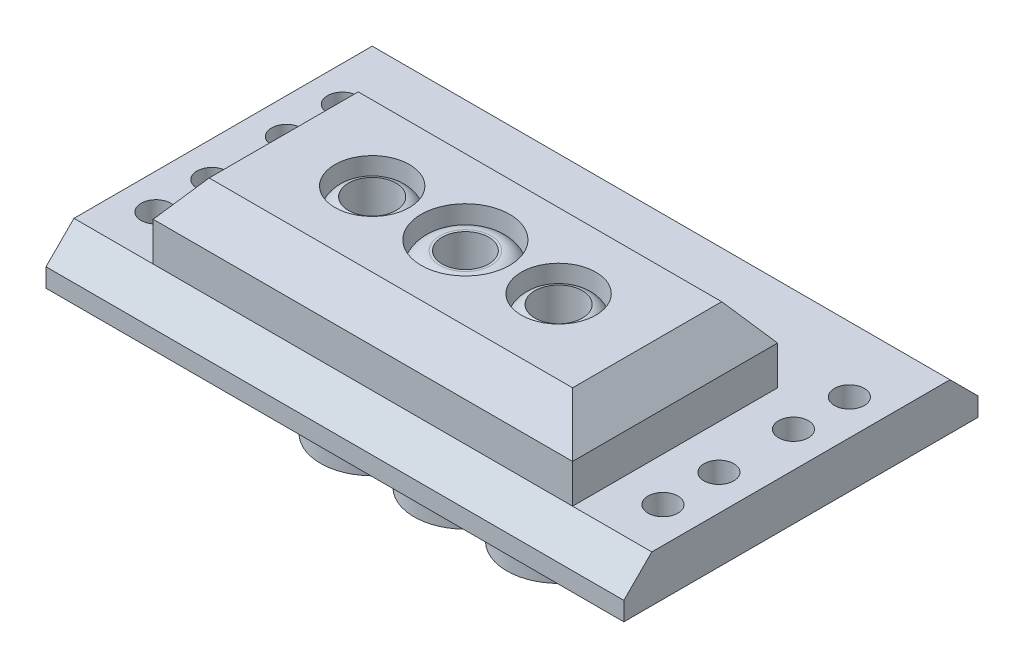
SolidWorks part; units mm, degrees
ref_plane "Alzado" through (0, 0, 0) normal (0, 0, 1) x (1, 0, 0)
ref_plane "Planta" through (0, 0, 0) normal (0, 1, 0) x (1, 0, 0)
ref_plane "Vista lateral" through (0, 0, 0) normal (1, 0, 0) x (0, 0, -1)
sketch "Croquis1" plane through (0, 0, 0) normal (0, 1, 0) x (1, 0, 0)
  line L0 (27.2, -5) -> (27.2, -11) construction
  line L1 (-31, -19) -> (31, -19)
  line L2 (-31, -19) -> (-31, 19)
  line L3 (-31, 19) -> (31, 19)
  line L4 (31, -19) -> (31, 19)
  line L5 (-31, -19) -> (31, 19) construction
  line L6 (-31, 19) -> (31, -19) construction
  line L7 (27.2, -11) -> (-27.2, -11) construction
  line L8 (-27.2, -5) -> (-27.2, -11) construction
  line L9 (27.2, 9) -> (27.2, 3) construction
  line L10 (27.2, 9) -> (27.2, 19) construction
  line L11 (27.2, 9) -> (31, 9) construction
  line L12 (-27.2, 9) -> (-27.2, 3) construction
  line L13 (-27.2, 9) -> (-27.2, 19) construction
  line L14 (0, 0) -> (0, -5) construction
  line L15 (-10, -5) -> (10, -5) construction
  circle A0 centre (27.2, -11) radius 1.6
  circle A1 centre (27.2, -5) radius 1.6
  circle A2 centre (-27.2, -11) radius 1.6
  circle A3 centre (-27.2, -5) radius 1.6
  circle A4 centre (27.2, 9) radius 1.6
  circle A5 centre (27.2, 3) radius 1.6
  circle A6 centre (-27.2, 3) radius 1.6
  circle A7 centre (-27.2, 9) radius 1.6
  circle A8 centre (0, -5) radius 2.5
  circle A9 centre (10, -5) radius 2.55
  circle A10 centre (-10, -5) radius 2.55
  point P0 (0, 0)
  point P31 (0, -5)
  dimension "D4" = 3.2
  dimension "D5" = 3.2
  dimension "D6" = 3.2
  dimension "D7" = 3.2
  dimension "D13" = 3.2
  dimension "D14" = 3.2
  dimension "D20" = 3.2
  dimension "D21" = 3.2
  dimension "D22" = 5
  dimension "D24" = 5.1
  dimension "D25" = 5.1
  dimension "D1" = 62
  dimension "D2" = 38
  dimension "D3" = 6
  dimension "D8" = 6
  dimension "D9" = 54.4
  dimension "D10" = 8
  dimension "D11" = 3.8
  dimension "D12" = 6
  dimension "D15" = 3.8
  dimension "D16" = 10
  dimension "D17" = 6
  dimension "D18" = 10
  dimension "D19" = 3.8
  dimension "D23" = 14
  dimension "D26" = 10
extrude "Saliente-Extruir1" add sketch "Croquis1" along normal blind 5
sketch "Croquis2" plane through (0, 5, 0) normal (0, 1, 0) x (1, 0, 0)
  line L0 (-31, -19) -> (31, -19) construction
  line L1 (0, -5) -> (0, 0) construction
  circle A0 centre (0, -5) radius 4.75
  circle A1 centre (0, -5) radius 2.5
  dimension "D2" = 9.5
  dimension "D3" = 5
  dimension "D1" = 14
extrude "Saliente-Extruir2" add sketch "Croquis2" along normal blind 7
fillet "Redondeo2" radius 2 1 edges at (0, 12, 9.75)
sketch "Croquis4" plane through (0, 5, 0) normal (0, 1, 0) x (1, 0, 0)
  line L0 (0, -5) -> (-10, -5) construction
  line L1 (0, -5) -> (10, -5) construction
  circle A0 centre (10, -5) radius 2.55
  circle A1 centre (-10, -5) radius 2.55
  circle A2 centre (-10, -5) radius 4
  circle A3 centre (10, -5) radius 4
  circle A4 centre (0, -5) radius 2.5 construction
  dimension "D1" = 5.1
  dimension "D2" = 5.1
  dimension "D5" = 8
  dimension "D6" = 8
  dimension "D3" = 10
  dimension "D4" = 10
extrude "Saliente-Extruir3" add sketch "Croquis4" along normal blind 7
fillet "Redondeo3" radius 2 2 edges at (-10, 12, 9) (10, 12, 9)
chamfer "Chaflán1" distance 3 angle 45 2 edges at (0, 5, -19) (0, 5, 19)
sketch "Croquis5" plane through (0, 5, 0) normal (0, 1, 0) x (1, 0, 0)
  line L1 (-22.5, 6) -> (22.5, 6)
  line L2 (-22.5, 6) -> (-22.5, -16)
  line L3 (-22.5, -16) -> (22.5, -16)
  line L4 (22.5, 6) -> (22.5, -16)
  line L5 (-22.5, 6) -> (22.5, -16) construction
  line L6 (-22.5, -16) -> (22.5, 6) construction
  line L7 (-16.5, 2) -> (16.5, 2)
  line L8 (-16.5, 2) -> (-16.5, -12)
  line L9 (-16.5, -12) -> (16.5, -12)
  line L10 (16.5, 2) -> (16.5, -12)
  line L11 (-16.5, 2) -> (16.5, -12) construction
  line L12 (-16.5, -12) -> (16.5, 2) construction
  point P0 (0, -5)
  point P6 (0, -5)
  point P11 (14.772, -10.5492)
  point P12 (16.017, -9.75)
  point P13 (16, -11.4926)
  point P17 (16, -9.7498)
  point P18 (16, -9.7498)
  circle M7 centre (-10, -5) radius 4
  circle M20 centre (0, -5) radius 4.75
  circle M21 centre (10, -5) radius 4
  dimension "D1" = 45
  dimension "D2" = 22
  dimension "D3" = 6
  dimension "D4" = 4
extrude "Saliente-Extruir4" add sketch "Croquis5" along normal blind 8 separate body contours L4 L1 L2 L3 L7 L10 L9 L8 | L8 L9 L7 M20 M7 | L10 L7 L9 M20 M21 region at (0, 5, -5.4991) region at (0, 5, -1.6415)
sketch "Croquis9" plane through (0, 0, 0) normal (0, -1, 0) x (1, 0, 0)
  line L0 (0, -6.6) -> (0, 6.6) construction
  circle A0 centre (0, 5) radius 5.5
  circle A1 centre (0, 5) radius 2.5 construction
  circle A2 centre (10, 5) radius 5.55
  circle A3 centre (10, 5) radius 2.55 construction
  circle A4 centre (-10, 5) radius 5.55
  circle M1 centre (10, 5) radius 2.55
  circle M14 centre (0, 5) radius 2.5
  circle M15 centre (-10, 5) radius 2.55
  dimension "D1" = 3
  dimension "D2" = 3
extrude "Saliente-Extruir7" add sketch "Croquis9" along normal blind 10 contours A0 A2 M1 | A0 A4 A2 M14 | A4 A0 M15 | A0 A2 | A4 A0 region at (4.9745, 0, 5) region at (5.5161, 0, 6.2381) region at (4.3017, 0, 5) region at (-4.9745, 0, 5) region at (-5.6533, 0, 5)
chamfer "Chaflán2" distance 3 angle 52 4 edges at (22.5, 13, 5) (-22.5, 13, 5) (0, 13, -6) (0, 13, 16) first distance on face at (0, 13, 5)
